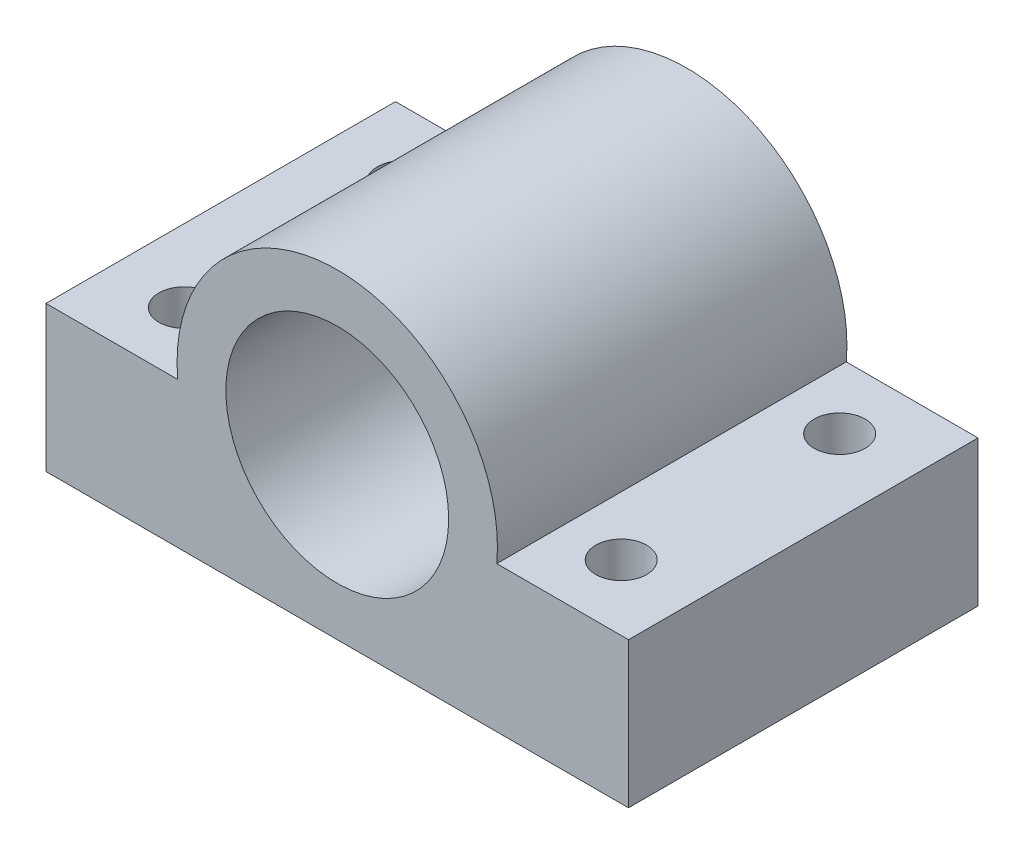
SolidWorks part; units mm, degrees
ref_plane "Plano frontal" through (0, 0, 0) normal (0, 0, 1) x (1, 0, 0)
ref_plane "Plano superior" through (0, 0, 0) normal (0, 1, 0) x (1, 0, 0)
ref_plane "Plano direito" through (0, 0, 0) normal (1, 0, 0) x (0, 0, -1)
sketch "Esboço1" plane through (0, 0, 0) normal (0, 0, 1) x (1, 0, 0)
  line L0 (-10.9545, -1) -> (-20, -1)
  line L1 (-20, -1) -> (-20, -11)
  line L2 (-20, -11) -> (0, -11)
  line L3 (0, -11) -> (20, -11)
  line L4 (20, -11) -> (20, -1)
  line L5 (20, -1) -> (10.9545, -1)
  circle A0 centre (0, 0) radius 7.65
  arc A1 (10.9545, -1) -> (-10.9545, -1) centre (0, 0) ccw
  point P3 (-18.1977, -11)
  point P10 (-10.5149, 3.2307)
  point P12 (10.6546, 2.735)
  point P13 (-9.8535, 4.8896)
  dimension "D1" = 11
  dimension "D2" = 15.3
  dimension "D3" = 40
  dimension "D4" = 10
extrude "Ressalto-extrusão1" add sketch "Esboço1" along normal blind 24
sketch "Esboço2" plane through (0, -11, 0) normal (0, -1, 0) x (1, 0, 0)
  line L0 (0, 0) -> (0, 24) construction
  line L1 (-20, 0) -> (20, 0) construction
  line L2 (-20, 24) -> (20, 24) construction
  line L3 (-20, 12) -> (20, 12) construction
  line L4 (-20, 24) -> (-20, 0) construction
  line L5 (20, 24) -> (20, 0) construction
  circle A0 centre (15, 19.5) radius 1.75
  circle A1 centre (15, 4.5) radius 1.75
  circle A2 centre (-15, 4.5) radius 1.75
  circle A3 centre (-15, 19.5) radius 1.75
  point P20 (0, 0)
  point P21 (0, 0)
  dimension "D3" = 3.5
  dimension "D1" = 15
  dimension "D2" = 30
extrude "Corte-extrusão1" cut sketch "Esboço2" against normal blind 20
